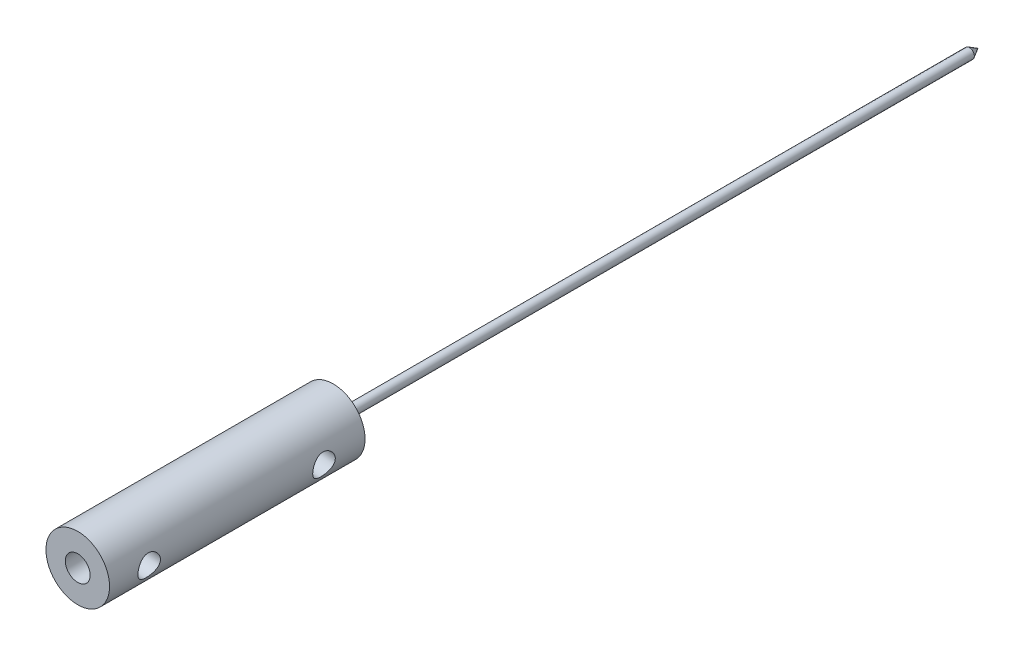
SolidWorks part; units mm, degrees
ref_plane "Front Plane" through (0, 0, 0) normal (0, 0, 1) x (1, 0, 0)
ref_plane "Top Plane" through (0, 0, 0) normal (0, 1, 0) x (1, 0, 0)
ref_plane "Right Plane" through (0, 0, 0) normal (1, 0, 0) x (0, 0, -1)
sketch "Sketch3" plane through (0, 0, 0) normal (0, 0, 1) x (1, 0, 0)
  circle A0 centre (0, 0) radius 3.2
  circle A1 centre (0, 0) radius 0.5
  dimension "D1" = 6.4
  dimension "D2" = 1
extrude "Boss-Extrude2" add sketch "Sketch3" along normal blind 25.7
sketch "Sketch6" plane through (0, 0, 25.7) normal (0, 0, 1) x (1, 0, 0)
  circle A0 centre (0, 0) radius 1.25
  circle M3 centre (0, 0) radius 0.5
  dimension "D1" = 2.5
extrude "Cut-Extrude1" cut sketch "Sketch6" against normal blind 25.7 and the other way through all
hole_wizard "Tap Drill for #4-40 Tap1" positions "3DSketch1" profile "Sketch8" hole size "#4-40" standard "ANSI Inch" end condition through all
sketch3d "3DSketch1"
  line L0 (3.1875, -0.2822, 21.7) -> (3.1875, -0.2822, 4.1124) construction
  point P0 (3.1875, -0.2822, 21.7)
  point P1 (3.1875, -0.2822, 4.1124)
  dimension "D1" = 4
sketch "Sketch8" plane through (3.1875, -0.2822, 21.7) normal (0, 0, 1) x (0.0882, 0.9961, 0)
  line L0 (0, 0) -> (0, 6.6698)
  line L1 (0, 6.6698) -> (1.1303, 6.6698)
  line L2 (1.1303, 6.6698) -> (1.1303, 0)
  line L5 (1.1303, 0) -> (0, 0)
  line L11 (0, -6.35) -> (0, 107.95) construction
  dimension "Thru Hole Dia." = 2.2606
  dimension "Thru Hole Depth" = 6.6698
extrude "Boss-Extrude4" add sketch "Sketch3<4>" against normal blind 69 from offset 5 separate body contours A1 region at (0, 0, 0)
sketch "Sketch3<4>" plane through (0, 0, 0) normal (0, 0, 1) x (1, 0, 0) same geometry as "Sketch3"
sketch "Sketch9" plane through (0, 0, 0) normal (0, 1, 0) x (1, 0, 0)
  line L0 (0, 64) -> (0, 64.866) construction
  line L1 (0, 64) -> (-0.5, 64)
  line L2 (-0.5, 64) -> (0, 64.866)
  line L3 (0.5, 64) -> (-0.5, 64) construction
  line L4 (0, 64) -> (0, 64.866)
  dimension "D1" = 30
revolve "Revolve1" add sketch "Sketch9" angle 360 about L0
extrude "Boss-Extrude5" add sketch "Sketch6<2>" along normal blind 5 from surface contours A0 M3 region at (-1.2146, 0, 25.7) starting at face at (1.25, 0, 0)
sketch "Sketch6<2>" plane through (0, 0, 25.7) normal (0, 0, 1) x (1, 0, 0) same geometry as "Sketch6"
